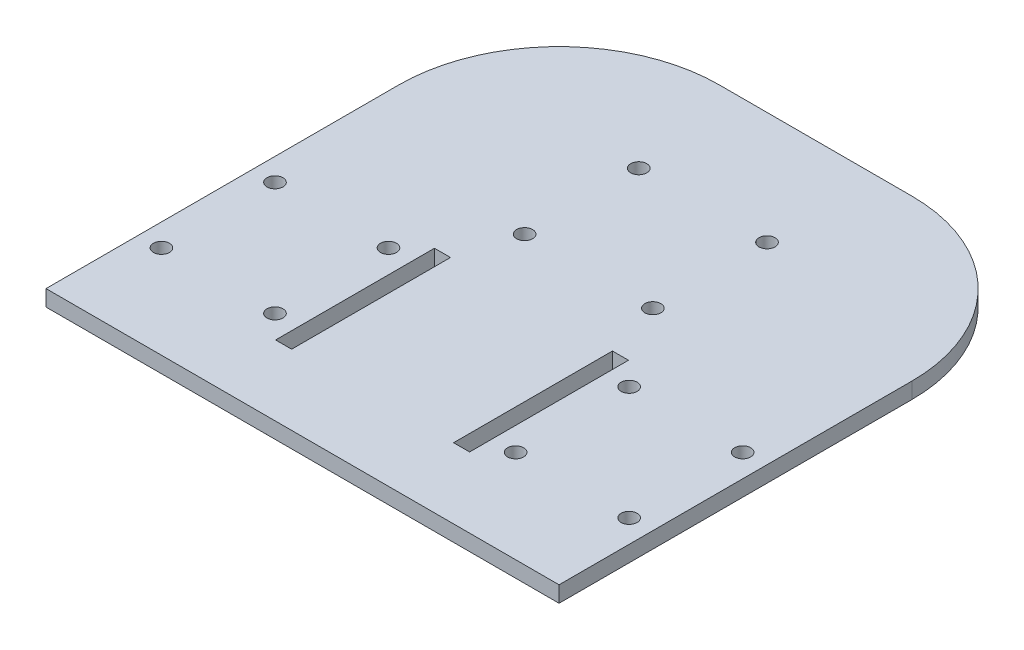
SolidWorks part; units mm, degrees
material "Acrylic (Medium-high impact)"
ref_plane "Front Plane" through (0, 0, 0) normal (0, 0, 1) x (1, 0, 0)
ref_plane "Top Plane" through (0, 0, 0) normal (0, 1, 0) x (1, 0, 0)
ref_plane "Right Plane" through (0, 0, 0) normal (1, 0, 0) x (0, 0, -1)
sketch "Sketch1" plane through (0, 0, 0) normal (0, 1, 0) x (1, 0, 0)
  line L1 (-101.6, -101.6) -> (101.6, -101.6)
  line L2 (-101.6, -101.6) -> (-101.6, 101.6)
  line L3 (-101.6, 101.6) -> (101.6, 101.6)
  line L4 (101.6, -101.6) -> (101.6, 101.6)
  line L5 (-101.6, -101.6) -> (101.6, 101.6) construction
  line L6 (-101.6, 101.6) -> (101.6, -101.6) construction
  point P0 (0, 0)
  dimension "D1" = 203.2
  dimension "D2" = 203.2
extrude "Boss-Extrude1" add sketch "Sketch1" along normal blind 6.35
sketch "Sketch2" plane through (0, 6.35, 0) normal (0, 1, 0) x (1, 0, 0)
  line L9 (101.6, 38.1) -> (101.6, 101.6)
  line L10 (101.6, 101.6) -> (38.1, 101.6)
  line L11 (-38.1, 101.6) -> (-101.6, 101.6)
  line L12 (-101.6, 101.6) -> (-101.6, 38.1)
  arc A2 (101.6, 38.1) -> (38.1, 101.6) centre (38.1, 38.1) ccw
  arc A3 (-101.6, 38.1) -> (-38.1, 101.6) centre (-38.1, 38.1) cw
extrude "Cut-Extrude1" cut sketch "Sketch2" against normal through all
sketch "Sketch9" plane through (0, 0, 0) normal (0, -1, 0) x (1, 0, 0)
  line L0 (-38.766, 10.8317) -> (-38.512, 10.8317) construction
  line L1 (-38.766, 73.756) -> (-38.512, 73.756) construction
  line L2 (38.5855, 10.8317) -> (38.3315, 10.8317) construction
  line L3 (-38.512, 10.8317) -> (-32.162, 10.8317)
  line L4 (-38.512, 10.8317) -> (-38.512, 73.756)
  line L5 (-38.512, 73.756) -> (-32.162, 73.756)
  line L6 (-32.162, 10.8317) -> (-32.162, 73.756)
  line L7 (38.5855, 73.756) -> (38.3315, 73.756) construction
  line L8 (-101.6, 101.6) -> (101.6, 101.6) construction
  line L13 (38.3315, 73.756) -> (31.9815, 73.756)
  line L14 (38.3315, 73.756) -> (38.3315, 10.8317)
  line L15 (38.3315, 10.8317) -> (31.9815, 10.8317)
  line L16 (31.9815, 73.756) -> (31.9815, 10.8317)
  line L17 (-101.6, -38.1) -> (-101.6, 101.6) construction
  circle A0 centre (-47.7463, 64.7757) radius 3.175
  circle A1 centre (-47.7463, 19.812) radius 3.175
  circle A2 centre (-92.71, 19.812) radius 3.175
  circle A3 centre (-92.71, 64.7757) radius 3.175
  circle A4 centre (-25.4903, -11.842) radius 3.175
  circle A5 centre (25.3097, -11.842) radius 3.175
  circle A6 centre (25.3097, -57.054) radius 3.175
  circle A7 centre (-25.4903, -57.054) radius 3.175
  circle A8 centre (47.5658, 19.812) radius 3.175
  circle A9 centre (92.5295, 19.812) radius 3.175
  circle A10 centre (92.5295, 64.7757) radius 3.175
  circle A11 centre (47.5658, 64.7757) radius 3.175
  point P2 (0, 0)
  point P5 (0, 0)
  point P8 (-223.8875, 133.4369)
  point P11 (-244.0852, 63.6677)
  point P52 (0, 0)
  point P53 (0, 0)
  dimension "D22" = 6.35
  dimension "D23" = 6.35
  dimension "D24" = 6.35
  dimension "D26" = 6.35
  dimension "D27" = 6.35
  dimension "D28" = 6.35
  dimension "D29" = 6.35
  dimension "D30" = 6.35
  dimension "D31" = 6.35
  dimension "D32" = 6.35
  dimension "D33" = 6.35
  dimension "D1" = 0.254
  dimension "D2" = 6.35
  dimension "D4" = 44.9637
  dimension "D5" = 63.5883
  dimension "D6" = 44.9637
  dimension "D7" = 54.6863
  dimension "D8" = 53.944
  dimension "D9" = 60.548
  dimension "D10" = 135.86
  dimension "D11" = 141.9453
  dimension "D12" = 125.0145
  dimension "D13" = 131.2955
  dimension "D14" = 140.2758
  dimension "D15" = 185.2395
  dimension "D16" = 190.6185
  dimension "D17" = 122.191
  dimension "D18" = 74.2999
  dimension "D19" = 102.1121
  dimension "D20" = 140.8441
  dimension "D21" = 3.175
  dimension "D25" = 147.3059
  dimension "D34" = 8.89
  dimension "D35" = 81.788
extrude "Cut-Extrude2" cut sketch "Sketch9" against normal through all
